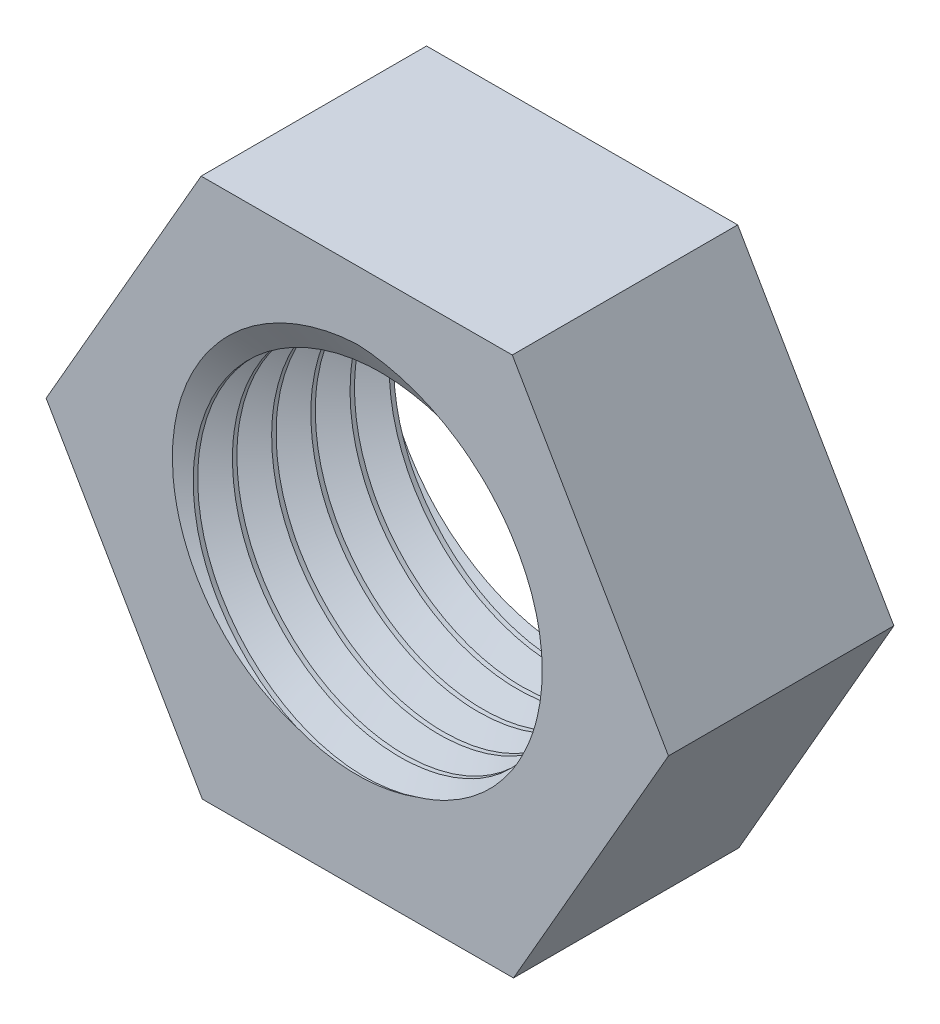
SolidWorks part; units mm, degrees
material "201 Annealed Stainless Steel (SS)"
ref_plane "Front Plane" through (0, 0, 0) normal (0, 0, 1) x (1, 0, 0)
ref_plane "Top Plane" through (0, 0, 0) normal (0, 1, 0) x (1, 0, 0)
ref_plane "Right Plane" through (0, 0, 0) normal (1, 0, 0) x (0, 0, -1)
sketch "Sketch1" plane through (0, 0, 0) normal (0, 0, 1) x (1, 0, 0)
  line L0 (-2.1489, -0.007) -> (2.2243, -0.007) construction
  line L1 (1.5937, -2.7465) -> (3.1754, 0.007)
  line L2 (3.1754, 0.007) -> (1.5817, 2.7535)
  line L3 (1.5817, 2.7535) -> (-1.5937, 2.7465)
  line L4 (-1.5937, 2.7465) -> (-3.1754, -0.007)
  line L5 (-3.1754, -0.007) -> (-1.5817, -2.7535)
  line L6 (-1.5817, -2.7535) -> (1.5937, -2.7465)
  circle A0 centre (0, 0) radius 2.75 construction
  circle A1 centre (0, 0) radius 1.75
  dimension "D2" = 5.5
  dimension "D1" = 3.5
  dimension "D3" = 0.126
extrude "Boss-Extrude1" add sketch "Sketch1" along normal blind 2.3
sketch "Sketch4" plane through (0, 0, 0) normal (0, 0, -1) x (-1, 0, 0)
  circle A0 centre (0, 0) radius 1.75
  dimension "D1" = 3.5
curve "Helix/Spiral1" pitch 0.4 height 3.5 turns 8.75
sketch "Sketch9" plane through (0, 0, 0) normal (1, 0, 0) x (0, 0, -1)
  line L1 (-3.5, 2.057) -> (-3.7598, 1.607)
  line L2 (-3.7598, 1.607) -> (-3.2402, 1.607)
  line L3 (-3.2402, 1.607) -> (-3.5, 2.057)
  line L4 (-2.3, 0.007) -> (0, 0.007) construction
  circle A0 centre (-3.5, 1.757) radius 0.15 construction
  dimension "D1" = 0.3
  dimension "D2" = 1.75
  dimension "D3" = 3.5
sweep "Cut-Sweep2" cut profiles "Sketch9" path "Helix/Spiral1"
sketch "Sketch10" plane through (0, 0, 0) normal (0, 0, -1) x (-1, 0, 0)
  circle A0 centre (0, 0) radius 2.5
  dimension "D1" = 5
